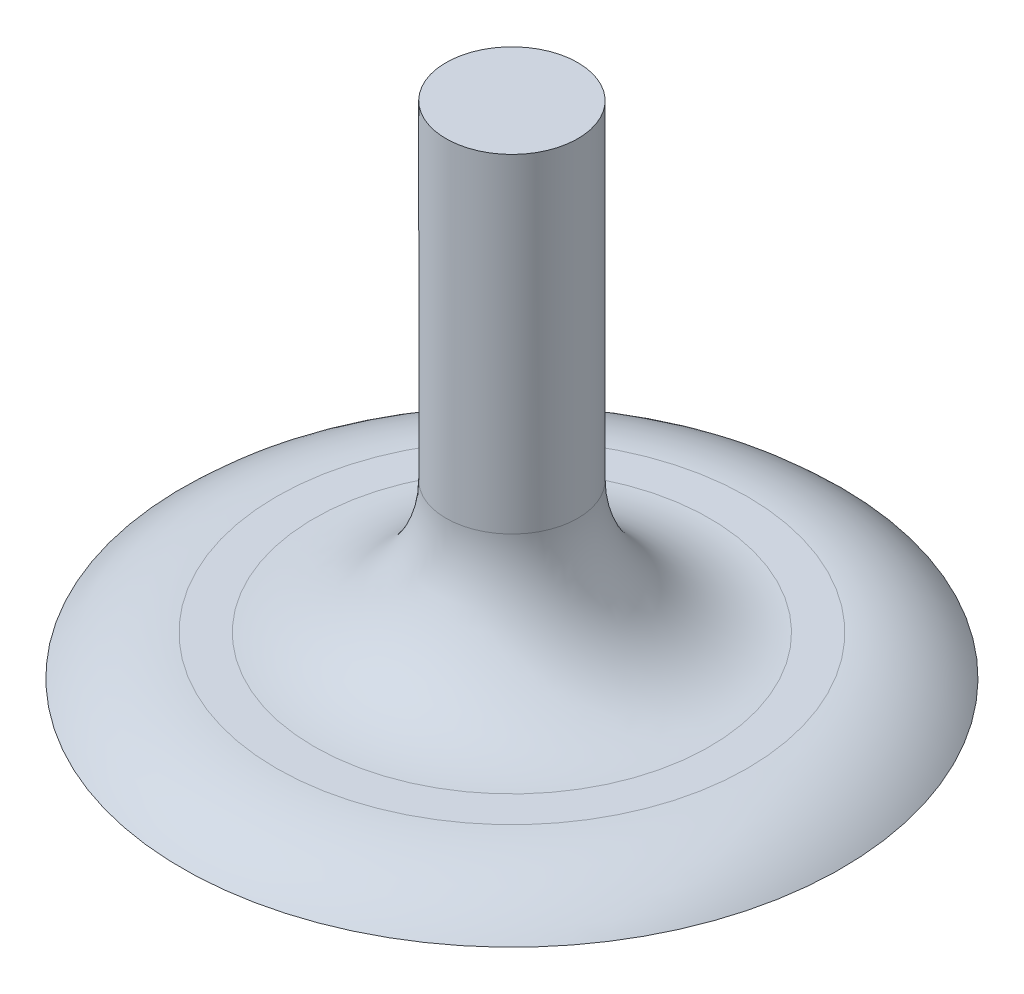
SolidWorks part; units mm, degrees
material "PS HI"
ref_plane "Front Plane" through (0, 0, 0) normal (0, 0, 1) x (1, 0, 0)
ref_plane "Top Plane" through (0, 0, 0) normal (0, 1, 0) x (1, 0, 0)
ref_plane "Right Plane" through (0, 0, 0) normal (1, 0, 0) x (0, 0, -1)
sketch "Sketch1" plane through (0, 0, 0) normal (1, 0, 0) x (0, 0, -1)
  line L0 (0, 0) -> (5, 10.7225)
  line L1 (0, 0) -> (0, 51.6595)
  line L2 (0, 55) -> (0, -55) construction
  line L3 (0, 51.6595) -> (5, 51.6595)
  line L4 (5, 51.6595) -> (5, 16.7225)
  line L5 (5, 16.7225) -> (25, 16.7225)
  line L6 (25, 16.7225) -> (25, 13.7225)
  line L7 (25, 13.7225) -> (5, 13.7225)
  line L8 (5, 13.7225) -> (5, 10.7225)
  dimension "D1" = 34.9369
  dimension "D2" = 5
  dimension "D3" = 25
  dimension "D4" = 3
  dimension "D5" = 25
  dimension "D6" = 3
revolve "Revolve1" add sketch "Sketch1" angle 360 about L1
fillet "Fillet1" radius 25 1 edges at (0, 13.7225, -5)
fillet "Fillet11" radius 25 rebuild error yes
dome "Dome1" faces to dome 1 distance 0.4 rebuild error yes parameters "D1"=0.4
fillet "Fillet12" radius 10 1 edges at (0, 16.7225, -5)
fillet "Fillet14" radius 10 1 edges at (0, 16.7225, -25)
